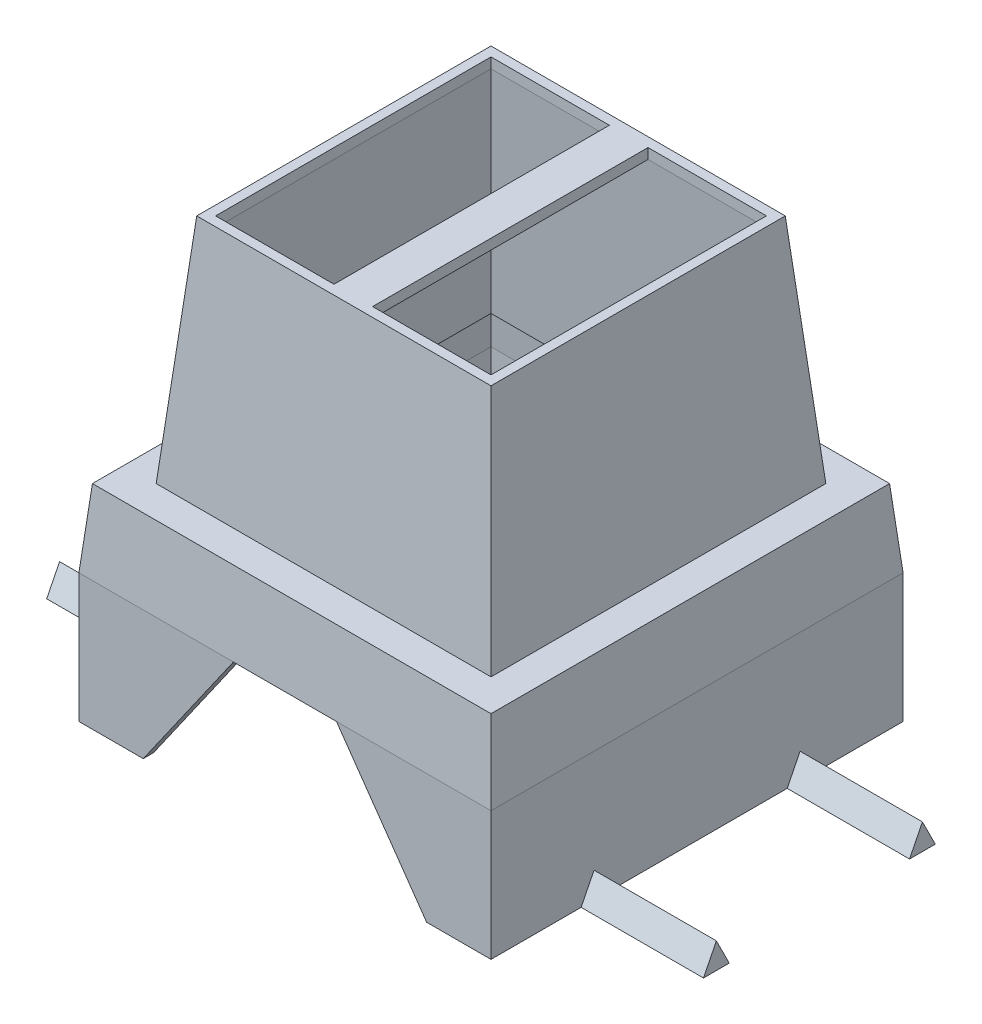
SolidWorks part; units mm, degrees
ref_plane "Front Plane" through (0, 0, 0) normal (0, 0, 1) x (1, 0, 0)
ref_plane "Top Plane" through (0, 0, 0) normal (0, 1, 0) x (1, 0, 0)
ref_plane "Right Plane" through (0, 0, 0) normal (1, 0, 0) x (0, 0, -1)
sketch "Sketch1" plane through (0, 0, 0) normal (0, 1, 0) x (1, 0, 0)
  line L13 (0, 0) -> (-32, 0)
  line L14 (0, 0) -> (0, 32)
  line L15 (0, 32) -> (-32, 32)
  line L16 (-32, 0) -> (-32, 32)
  dimension "D1" = 32
  dimension "D2" = 32
extrude "Boss-Extrude1" add sketch "Sketch1" along normal blind 6 draft 5
sketch "Sketch2" plane through (0, 6, 0) normal (0, 1, 0) x (1, 0, 0)
  line L0 (-31.4751, 0.5249) -> (-0.5249, 0.5249) construction
  line L1 (-29, 29) -> (-3, 29)
  line L2 (-29, 29) -> (-29, 3)
  line L3 (-29, 3) -> (-3, 3)
  line L4 (-3, 29) -> (-3, 3)
  line L5 (-0.5249, 0.5249) -> (-0.5249, 31.4751) construction
  point P5 (-16, 3)
  point P8 (-16, 0.5249)
  point P9 (-3, 16)
  point P12 (-0.5249, 16)
  dimension "D1" = 26
  dimension "D2" = 26
extrude "Boss-Extrude2" add sketch "Sketch2" along normal blind 18 draft 5
shell "Shell1" thickness 0.8 removed face at (-16, 0, -16)
chamfer "Chamfer1" distance 2.5 angle 45 4 edges at (-16, 5.2, -1.258) (-30.742, 5.2, -16) (-16, 5.2, -30.742) (-1.258, 5.2, -16) first distance on face at (-16, 5.2, -16)
sketch "Sketch3" plane through (0, 23.2, 0) normal (0, -1, 0) x (1, 0, 0)
  line L0 (-5.3079, -26.6921) -> (-26.6921, -26.6921) construction
  line L1 (-17.5, -5.3079) -> (-14.5, -5.3079)
  line L2 (-17.5, -5.3079) -> (-17.5, -26.6921)
  line L3 (-17.5, -26.6921) -> (-14.5, -26.6921)
  line L4 (-14.5, -5.3079) -> (-14.5, -26.6921)
  line L5 (-26.6921, -5.3079) -> (-5.3079, -5.3079) construction
  line L7 (-17.5, -5.3079) -> (-26.6921, -5.3079)
  line L8 (-17.5, -5.3079) -> (-17.5, -26.6921)
  line L9 (-17.5, -26.6921) -> (-26.6921, -26.6921)
  line L10 (-26.6921, -5.3079) -> (-26.6921, -26.6921)
  line L11 (-14.5, -5.3079) -> (-5.3079, -5.3079)
  line L12 (-14.5, -5.3079) -> (-14.5, -26.6921)
  line L13 (-14.5, -26.6921) -> (-5.3079, -26.6921)
  line L14 (-5.3079, -5.3079) -> (-5.3079, -26.6921)
  point P6 (-16, -5.3079)
  point P9 (-16, -5.3079)
  line M13 (-26.6921, -5.3079) -> (-26.6921, -26.6921)
  line M14 (-26.6921, -26.6921) -> (-5.3079, -26.6921)
  line M15 (-5.3079, -26.6921) -> (-5.3079, -5.3079)
  line M16 (-5.3079, -5.3079) -> (-26.6921, -5.3079)
  dimension "D1" = 3
extrude "Cut-Extrude1" cut sketch "Sketch3" against normal through all contours L2 M16 M13 M14 | L4 M16 M14 M15 region at (-22.0961, 23.2, -16) region at (-9.9039, 23.2, -16)
sketch "Sketch4" plane through (0, 0, 0) normal (0, -1, 0) x (1, 0, 0)
  line L1 (-32, 0) -> (0, 0)
  line L2 (-32, 0) -> (-32, -32)
  line L3 (-32, -32) -> (0, -32)
  line L4 (0, 0) -> (0, -32)
  line L5 (-0.8031, -31.1969) -> (-31.1969, -31.1969)
  line L6 (-0.8031, -31.1969) -> (-0.8031, -0.8031)
  line L7 (-0.8031, -0.8031) -> (-31.1969, -0.8031)
  line L8 (-31.1969, -31.1969) -> (-31.1969, -0.8031)
extrude "Boss-Extrude3" add sketch "Sketch4" along normal blind 10
sketch "Sketch5" plane through (-32, 0, 0) normal (-1, 0, 0) x (0, 0, 1)
  line L0 (-25, -10) -> (-23, -10)
  line L1 (0, -10) -> (-32, -10) construction
  line L2 (-23, -10) -> (-24, -8)
  line L3 (-24, -8) -> (-25, -10)
  line L4 (-9, -10) -> (-7, -10)
  line L5 (-7, -10) -> (-8, -8)
  line L6 (-8, -8) -> (-9, -10)
  line L7 (-23, -10) -> (-9, -10)
  point P7 (-16, -10)
  point P9 (-24, -10)
  point P10 (-12.8638, -10)
  point P12 (-16, -10)
  point P13 (0, 0)
  point P14 (-12.7902, -10)
  line M10 (-32, -10) -> (0, -10)
  dimension "D1" = 14
  dimension "D2" = 2
  dimension "D3" = 2
extrude "Boss-Extrude4" add sketch "Sketch5" along normal blind 9.5 contours L2 L3 M10 | L5 L6 M10 region at (-32, -9.3333, -24) region at (-32, -9.3333, -8)
extrude "Boss-Extrude5" add sketch "Sketch5<3>" against normal blind 9.5 from surface contours L5 L6 M10 | L2 L3 M10 region at (-32, -9.3333, -24) region at (-32, -9.3333, -8) starting at face at (0, -5, -16)
sketch "Sketch5<3>" plane through (-32, 0, 0) normal (-1, 0, 0) x (0, 0, 1) same geometry as "Sketch5"
sketch "Sketch6" plane through (0, 0, -32) normal (0, 0, -1) x (-1, 0, 0)
  line L0 (12, 0) -> (4.9979, -10)
  line L1 (0, 0) -> (32, 0) construction
  line L2 (32, -10) -> (0, -10) construction
  line L3 (4.9979, -10) -> (27.0021, -10)
  line L4 (27.0021, -10) -> (20, 0)
  line L5 (20, 0) -> (12, 0)
  point P6 (16, 0)
  point P9 (16, -10)
  point P10 (8.7159, 0)
  point P11 (14.1554, 0)
  point P12 (15.4086, 0)
  point P13 (33.1618, 0)
  point P14 (16, 0)
  dimension "D1" = 55
  dimension "D2" = 8
extrude "Cut-Extrude2" cut sketch "Sketch6" against normal through all
equation "\"D2@Sketch1\"=\"D1@Sketch1\""
equation "\"D2@Sketch2\"=\"D1@Sketch2\""
